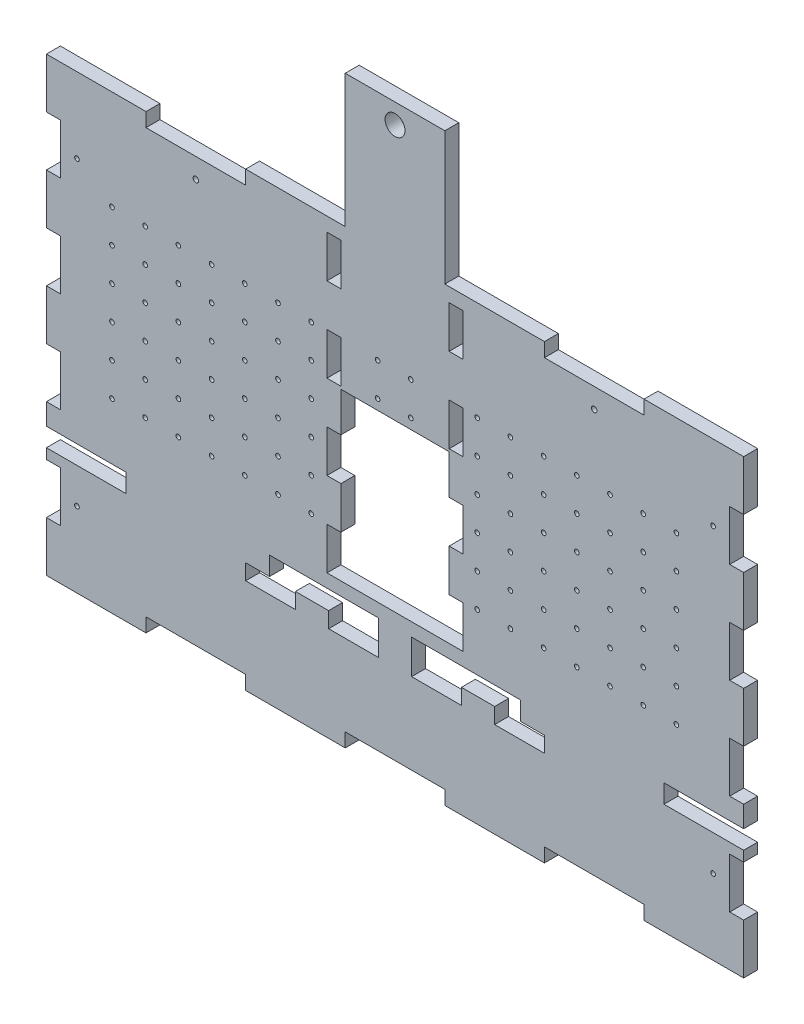
SolidWorks part; units mm, degrees
ref_plane "Front Plane" through (0, 0, 0) normal (0, 0, 1) x (1, 0, 0)
ref_plane "Top Plane" through (0, 0, 0) normal (0, 1, 0) x (1, 0, 0)
ref_plane "Right Plane" through (0, 0, 0) normal (1, 0, 0) x (0, 0, -1)
sketch "Sketch1" plane through (0, 0, 0) normal (0, 0, 1) x (1, 0, 0)
  line L1 (-127.8759, 88.4641) -> (138.8241, 88.4641)
  line L2 (-127.8759, 88.4641) -> (-127.8759, -84.2559)
  line L3 (-127.8759, -84.2559) -> (138.8241, -84.2559)
  line L4 (138.8241, 88.4641) -> (138.8241, -84.2559)
  dimension "D1" = 266.7
  dimension "D2" = 172.72
extrude "Boss-Extrude1" add sketch "Sketch1" along normal blind 5.334
sketch "Sketch2" plane through (0, 0, 5.334) normal (0, 0, 1) x (1, 0, 0)
  line L0 (-127.8759, -84.2559) -> (138.8241, -84.2559) construction
  line L1 (-89.7759, -84.2559) -> (-51.6759, -84.2559)
  line L2 (-89.7759, -84.2559) -> (-89.7759, -78.9219)
  line L3 (-89.7759, -78.9219) -> (-51.6759, -78.9219)
  line L4 (-51.6759, -84.2559) -> (-51.6759, -78.9219)
  line L5 (-89.7759, -78.9219) -> (-127.8759, -78.9219) construction
  line L6 (-13.5759, -84.2559) -> (24.5241, -84.2559)
  line L7 (-13.5759, -84.2559) -> (-13.5759, -78.9219)
  line L8 (-13.5759, -78.9219) -> (24.5241, -78.9219)
  line L9 (24.5241, -84.2559) -> (24.5241, -78.9219)
  line L10 (62.6241, -84.2559) -> (100.7241, -84.2559)
  line L11 (62.6241, -84.2559) -> (62.6241, -78.9219)
  line L12 (62.6241, -78.9219) -> (100.7241, -78.9219)
  line L13 (100.7241, -84.2559) -> (100.7241, -78.9219)
  line L14 (-127.8759, 88.4641) -> (-127.8759, -84.2559) construction
  line L15 (-51.6759, -78.9219) -> (-13.5759, -78.9219) construction
  line L16 (24.5241, -78.9219) -> (62.6241, -78.9219) construction
  line L17 (62.6241, -78.9219) -> (62.364, -79.7896) construction
  line L18 (100.7241, -78.9219) -> (138.8241, -78.9219) construction
  line L19 (138.8241, -84.2559) -> (138.8241, 88.4641) construction
  line L20 (-127.8759, 2.1041) -> (138.8241, 2.1041) construction
  line L21 (100.7241, 88.4641) -> (100.7241, 83.1301)
  line L22 (62.6241, 83.1301) -> (100.7241, 83.1301)
  line L23 (62.6241, 88.4641) -> (62.6241, 83.1301)
  line L24 (24.5241, 88.4641) -> (24.5241, 83.1301)
  line L25 (-13.5759, 83.1301) -> (24.5241, 83.1301)
  line L26 (-13.5759, 88.4641) -> (-13.5759, 83.1301)
  line L27 (-51.6759, 88.4641) -> (-51.6759, 83.1301)
  line L28 (-89.7759, 83.1301) -> (-51.6759, 83.1301)
  line L29 (-89.7759, 88.4641) -> (-89.7759, 83.1301)
  line L30 (62.6241, 88.4641) -> (100.7241, 88.4641)
  line L31 (-13.5759, 88.4641) -> (24.5241, 88.4641)
  line L32 (-89.7759, 88.4641) -> (-51.6759, 88.4641)
  dimension "D1" = 5.334
extrude "Cut-Extrude1" cut sketch "Sketch2" against normal through all
sketch "Sketch5" plane through (0, 0, 5.334) normal (0, 0, 1) x (1, 0, 0)
  line L0 (5.4741, 83.1301) -> (5.4741, -78.9219) construction
  line L1 (-13.5759, 83.1301) -> (24.5241, 83.1301) construction
  line L2 (24.5241, -78.9219) -> (-13.5759, -78.9219) construction
  line L3 (11.8241, -34.8224) -> (11.8241, -41.9344)
  line L4 (-42.5319, -34.8224) -> (-0.8759, -34.8224)
  line L5 (-42.5319, -34.8224) -> (-42.5319, -41.9344)
  line L6 (-42.5319, -41.9344) -> (-0.8759, -41.9344)
  line L7 (-0.8759, -34.8224) -> (-0.8759, -41.9344)
  line L8 (53.4801, -41.9344) -> (11.8241, -41.9344)
  line L9 (53.4801, -34.8224) -> (53.4801, -41.9344)
  line L10 (53.4801, -34.8224) -> (11.8241, -34.8224)
  line L11 (11.8241, -34.8224) -> (-0.8759, -34.8224) construction
  line L12 (-0.8759, -41.9344) -> (11.8241, -41.9344) construction
  line L13 (-139.0519, -34.8224) -> (-97.3959, -34.8224)
  line L14 (-139.0519, -34.8224) -> (-139.0519, -41.9344)
  line L15 (-139.0519, -41.9344) -> (-97.3959, -41.9344)
  line L16 (-97.3959, -34.8224) -> (-97.3959, -41.9344)
  line L18 (108.3441, -34.8224) -> (108.3441, -41.9344)
  line L19 (150.0001, -41.9344) -> (108.3441, -41.9344)
  line L20 (150.0001, -34.8224) -> (150.0001, -41.9344)
  line L21 (150.0001, -34.8224) -> (108.3441, -34.8224)
  dimension "D2" = 41.656
  dimension "D3" = 6.35
  dimension "D1" = 7.112
  dimension "D4" = 2
extrude "Cut-Extrude3" cut sketch "Sketch5" against normal through all
sketch "Sketch9" plane through (0, 0, 5.334) normal (0, 0, 1) x (1, 0, 0)
  line L0 (-127.8759, 88.4641) -> (-127.8759, -34.8224) construction
  line L1 (-127.8759, -65.0647) -> (-122.5419, -65.0647)
  line L2 (-127.8759, -65.0647) -> (-127.8759, -45.8736)
  line L3 (-127.8759, -45.8736) -> (-122.5419, -45.8736)
  line L4 (-122.5419, -65.0647) -> (-122.5419, -45.8736)
  line L5 (-122.5419, 69.273) -> (-122.5419, 88.4641) construction
  line L6 (-127.8759, -26.6825) -> (-122.5419, -26.6825)
  line L7 (-127.8759, -26.6825) -> (-127.8759, -7.4914)
  line L8 (-127.8759, -7.4914) -> (-122.5419, -7.4914)
  line L9 (-122.5419, -26.6825) -> (-122.5419, -7.4914)
  line L10 (-127.8759, 11.6997) -> (-122.5419, 11.6997)
  line L11 (-127.8759, 11.6997) -> (-127.8759, 30.8908)
  line L12 (-127.8759, 30.8908) -> (-122.5419, 30.8908)
  line L13 (-122.5419, 11.6997) -> (-122.5419, 30.8908)
  line L14 (-127.8759, 50.0819) -> (-122.5419, 50.0819)
  line L15 (-127.8759, 50.0819) -> (-127.8759, 69.273)
  line L16 (-127.8759, 69.273) -> (-122.5419, 69.273)
  line L17 (-122.5419, 50.0819) -> (-122.5419, 69.273)
  line L18 (-89.7759, 88.4641) -> (-127.8759, 88.4641) construction
  line L19 (-122.5419, 50.0819) -> (-122.5419, 30.8908) construction
  line L20 (-122.5419, 11.6997) -> (-122.5419, -7.4914) construction
  line L21 (-122.5419, -26.6825) -> (-122.5419, -45.8736) construction
  line L22 (-122.5419, -65.0647) -> (-122.5419, -84.2559) construction
  line L23 (-127.8759, -84.2559) -> (-89.7759, -84.2559) construction
  line L24 (5.4741, 83.1301) -> (5.4741, -78.9219) construction
  line L25 (-13.5759, 83.1301) -> (24.5241, 83.1301) construction
  line L26 (24.5241, -78.9219) -> (-13.5759, -78.9219) construction
  line L27 (133.4901, -65.0647) -> (133.4901, -84.2559) construction
  line L28 (133.4901, -26.6825) -> (133.4901, -45.8736) construction
  line L29 (133.4901, 11.6997) -> (133.4901, -7.4914) construction
  line L30 (133.4901, 50.0819) -> (133.4901, 30.8908) construction
  line L31 (133.4901, 69.273) -> (133.4901, 88.4641) construction
  line L32 (133.4901, 50.0819) -> (133.4901, 69.273)
  line L33 (138.8241, 69.273) -> (133.4901, 69.273)
  line L34 (138.8241, 50.0819) -> (138.8241, 69.273)
  line L35 (138.8241, 50.0819) -> (133.4901, 50.0819)
  line L36 (133.4901, 11.6997) -> (133.4901, 30.8908)
  line L37 (138.8241, 30.8908) -> (133.4901, 30.8908)
  line L38 (138.8241, 11.6997) -> (138.8241, 30.8908)
  line L39 (138.8241, 11.6997) -> (133.4901, 11.6997)
  line L40 (133.4901, -26.6825) -> (133.4901, -7.4914)
  line L41 (138.8241, -7.4914) -> (133.4901, -7.4914)
  line L42 (138.8241, -26.6825) -> (138.8241, -7.4914)
  line L43 (138.8241, -26.6825) -> (133.4901, -26.6825)
  line L44 (133.4901, -65.0647) -> (133.4901, -45.8736)
  line L45 (138.8241, -45.8736) -> (133.4901, -45.8736)
  line L46 (138.8241, -65.0647) -> (138.8241, -45.8736)
  line L47 (138.8241, -65.0647) -> (133.4901, -65.0647)
  dimension "D1" = 5.334
extrude "Cut-Extrude7" cut sketch "Sketch9" against normal through all
sketch "Sketch10" plane through (0, 88.4641, 0) normal (0, 1, 0) x (1, 0, 0)
  line L1 (24.5241, -5.334) -> (62.6241, -5.334)
  line L2 (24.5241, -5.334) -> (24.5241, 0)
  line L3 (24.5241, 0) -> (62.6241, 0)
  line L4 (62.6241, -5.334) -> (62.6241, 0)
extrude "Boss-Extrude2" add sketch "Sketch10" along normal blind 50.8
sketch "Sketch11" plane through (0, 0, 0) normal (0, 0, -1) x (-1, 0, 0)
  line L0 (-24.5241, 83.1301) -> (-24.5241, 139.2641) construction
  line L1 (-24.5241, 88.4641) -> (-31.1281, 88.4641)
  line L2 (-24.5241, 88.4641) -> (-24.5241, 129.1041)
  line L3 (-24.5241, 129.1041) -> (-31.1281, 129.1041)
  line L4 (-31.1281, 88.4641) -> (-31.1281, 129.1041)
  line L5 (13.5759, 88.4641) -> (51.6759, 88.4641) construction
  dimension "D1" = 6.604
  dimension "D3" = 0
extrude "Cut-Extrude8" cut sketch "Sketch11" against normal through all
sketch "Sketch12" plane through (0, 0, 5.334) normal (0, 0, 1) x (1, 0, 0)
  line L0 (62.6241, 139.2641) -> (62.6241, 83.1301) construction
  circle A0 centre (43.5741, 130.4765) radius 3.81
  dimension "D1" = 19.05
extrude "Cut-Extrude9" cut sketch "Sketch12" against normal through all
sketch "Sketch14" plane through (0, 0, 5.334) normal (0, 0, 1) x (1, 0, 0)
  line L0 (-89.7759, 88.4641) -> (-127.8759, 88.4641) construction
  circle A0 centre (-102.7976, 50.3641) radius 0.889
  circle A1 centre (-90.0976, 50.3641) radius 0.889
  circle A2 centre (-77.3976, 50.3641) radius 0.889
  circle A3 centre (-64.6976, 50.3641) radius 0.889
  circle A4 centre (-51.9976, 50.3641) radius 0.889
  circle A5 centre (-39.2976, 50.3641) radius 0.889
  circle A6 centre (-26.5976, 50.3641) radius 0.889
  circle A8 centre (-1.1976, 50.3641) radius 0.889
  circle A9 centre (11.5024, 50.3641) radius 0.889
  circle A11 centre (36.9024, 50.3641) radius 0.889
  circle A12 centre (49.6024, 50.3641) radius 0.889
  circle A13 centre (62.3024, 50.3641) radius 0.889
  circle A14 centre (75.0024, 50.3641) radius 0.889
  circle A15 centre (87.7024, 50.3641) radius 0.889
  circle A16 centre (100.4024, 50.3641) radius 0.889
  circle A17 centre (113.1024, 50.3641) radius 0.889
  circle A18 centre (-102.7976, 37.6641) radius 0.889
  circle A19 centre (-90.0976, 37.6641) radius 0.889
  circle A20 centre (-77.3976, 37.6641) radius 0.889
  circle A21 centre (-64.6976, 37.6641) radius 0.889
  circle A22 centre (-51.9976, 37.6641) radius 0.889
  circle A23 centre (-39.2976, 37.6641) radius 0.889
  circle A24 centre (-26.5976, 37.6641) radius 0.889
  circle A26 centre (-1.1976, 37.6641) radius 0.889
  circle A27 centre (11.5024, 37.6641) radius 0.889
  circle A29 centre (36.9024, 37.6641) radius 0.889
  circle A30 centre (49.6024, 37.6641) radius 0.889
  circle A31 centre (62.3024, 37.6641) radius 0.889
  circle A32 centre (75.0024, 37.6641) radius 0.889
  circle A33 centre (87.7024, 37.6641) radius 0.889
  circle A34 centre (100.4024, 37.6641) radius 0.889
  circle A35 centre (113.1024, 37.6641) radius 0.889
  circle A36 centre (-102.7976, 24.9641) radius 0.889
  circle A37 centre (-90.0976, 24.9641) radius 0.889
  circle A38 centre (-77.3976, 24.9641) radius 0.889
  circle A39 centre (-64.6976, 24.9641) radius 0.889
  circle A40 centre (-51.9976, 24.9641) radius 0.889
  circle A41 centre (-39.2976, 24.9641) radius 0.889
  circle A42 centre (-26.5976, 24.9641) radius 0.889
  circle A44 centre (-1.1976, 24.9641) radius 0.889
  circle A45 centre (11.5024, 24.9641) radius 0.889
  circle A47 centre (36.9024, 24.9641) radius 0.889
  circle A48 centre (49.6024, 24.9641) radius 0.889
  circle A49 centre (62.3024, 24.9641) radius 0.889
  circle A50 centre (75.0024, 24.9641) radius 0.889
  circle A51 centre (87.7024, 24.9641) radius 0.889
  circle A52 centre (100.4024, 24.9641) radius 0.889
  circle A53 centre (113.1024, 24.9641) radius 0.889
  circle A54 centre (-102.7976, 12.2641) radius 0.889
  circle A55 centre (-90.0976, 12.2641) radius 0.889
  circle A56 centre (-77.3976, 12.2641) radius 0.889
  circle A57 centre (-64.6976, 12.2641) radius 0.889
  circle A58 centre (-51.9976, 12.2641) radius 0.889
  circle A59 centre (-39.2976, 12.2641) radius 0.889
  circle A60 centre (-26.5976, 12.2641) radius 0.889
  circle A65 centre (36.9024, 12.2641) radius 0.889
  circle A66 centre (49.6024, 12.2641) radius 0.889
  circle A67 centre (62.3024, 12.2641) radius 0.889
  circle A68 centre (75.0024, 12.2641) radius 0.889
  circle A69 centre (87.7024, 12.2641) radius 0.889
  circle A70 centre (100.4024, 12.2641) radius 0.889
  circle A71 centre (113.1024, 12.2641) radius 0.889
  circle A72 centre (-102.7976, -0.4359) radius 0.889
  circle A73 centre (-90.0976, -0.4359) radius 0.889
  circle A74 centre (-77.3976, -0.4359) radius 0.889
  circle A75 centre (-64.6976, -0.4359) radius 0.889
  circle A76 centre (-51.9976, -0.4359) radius 0.889
  circle A77 centre (-39.2976, -0.4359) radius 0.889
  circle A78 centre (-26.5976, -0.4359) radius 0.889
  circle A79 centre (-13.8976, -0.4359) radius 0.889
  circle A80 centre (-1.1976, -0.4359) radius 0.889
  circle A81 centre (11.5024, -0.4359) radius 0.889
  circle A82 centre (24.2024, -0.4359) radius 0.889
  circle A83 centre (36.9024, -0.4359) radius 0.889
  circle A84 centre (49.6024, -0.4359) radius 0.889
  circle A85 centre (62.3024, -0.4359) radius 0.889
  circle A86 centre (75.0024, -0.4359) radius 0.889
  circle A87 centre (87.7024, -0.4359) radius 0.889
  circle A88 centre (100.4024, -0.4359) radius 0.889
  circle A89 centre (113.1024, -0.4359) radius 0.889
  circle A90 centre (-102.7976, -13.1359) radius 0.889
  circle A91 centre (-90.0976, -13.1359) radius 0.889
  circle A92 centre (-77.3976, -13.1359) radius 0.889
  circle A93 centre (-64.6976, -13.1359) radius 0.889
  circle A94 centre (-51.9976, -13.1359) radius 0.889
  circle A95 centre (-39.2976, -13.1359) radius 0.889
  circle A96 centre (-26.5976, -13.1359) radius 0.889
  circle A97 centre (-13.8976, -13.1359) radius 0.889
  circle A98 centre (-1.1976, -13.1359) radius 0.889
  circle A99 centre (11.5024, -13.1359) radius 0.889
  circle A100 centre (24.2024, -13.1359) radius 0.889
  circle A101 centre (36.9024, -13.1359) radius 0.889
  circle A102 centre (49.6024, -13.1359) radius 0.889
  circle A103 centre (62.3024, -13.1359) radius 0.889
  circle A104 centre (75.0024, -13.1359) radius 0.889
  circle A105 centre (87.7024, -13.1359) radius 0.889
  circle A106 centre (100.4024, -13.1359) radius 0.889
  circle A107 centre (113.1024, -13.1359) radius 0.889
  circle A108 centre (-1.1976, 12.2641) radius 0.889 [skipped]
  circle A110 centre (11.5024, 12.2641) radius 0.889 [skipped]
  circle A116 centre (24.2024, 50.3641) radius 0.889 [skipped]
  circle A117 centre (-13.8976, 50.3641) radius 0.889 [skipped]
  dimension "D1" = 18
  dimension "D2" = 38.1
  dimension "D4" = 1.778
  dimension "D3" = 6
extrude "Cut-Extrude11" cut sketch "Sketch14" against normal through all
sketch "Sketch15" plane through (0, 0, 5.334) normal (0, 0, 1) x (1, 0, 0)
  line L1 (31.1281, 129.1041) -> (24.5241, 129.1041)
  line L2 (31.1281, 129.1041) -> (31.1281, 139.2641)
  line L3 (31.1281, 139.2641) -> (24.5241, 139.2641)
  line L4 (24.5241, 129.1041) -> (24.5241, 139.2641)
extrude "Cut-Extrude12" cut sketch "Sketch15" against normal through all
sketch "Sketch16" plane through (0, 0, 5.334) normal (0, 0, 1) x (1, 0, 0)
  line L0 (5.4741, 83.1301) -> (5.4741, -78.9219) construction
  line L1 (-15.2269, 33.7576) -> (26.1751, 33.7576)
  line L2 (-15.2269, 33.7576) -> (-15.2269, -29.7424)
  line L3 (-15.2269, -29.7424) -> (26.1751, -29.7424)
  line L4 (26.1751, 33.7576) -> (26.1751, -29.7424)
  line L5 (-13.5759, 83.1301) -> (24.5241, 83.1301) construction
  line L6 (24.5241, -78.9219) -> (-13.5759, -78.9219) construction
  line L8 (-0.8759, -34.8224) -> (-42.5319, -34.8224) construction
  dimension "D1" = 63.5
  dimension "D2" = 41.402
  dimension "D3" = 20.701
  dimension "D4" = 5.08
extrude "Cut-Extrude13" cut sketch "Sketch16" against normal through all
sketch "Sketch17" plane through (0, 0, 5.334) normal (0, 0, 1) x (1, 0, 0)
  line L0 (-15.2269, 33.7576) -> (-15.2269, -29.7424) construction
  line L1 (-15.2269, -29.7424) -> (-20.5609, -29.7424)
  line L2 (-15.2269, -29.7424) -> (-15.2269, -13.6178)
  line L3 (-15.2269, -13.6178) -> (-20.5609, -13.6178)
  line L4 (-20.5609, -29.7424) -> (-20.5609, -13.6178)
  line L5 (-15.2269, 2.5069) -> (-20.5609, 2.5069)
  line L6 (-15.2269, 2.5069) -> (-15.2269, 18.6315)
  line L7 (-15.2269, 18.6315) -> (-20.5609, 18.6315)
  line L8 (-20.5609, 2.5069) -> (-20.5609, 18.6315)
  line L9 (-20.5609, -13.6178) -> (-20.5609, 2.5069) construction
  line L10 (-20.5609, 50.8808) -> (-15.2269, 50.8808)
  line L11 (-20.5609, 50.8808) -> (-20.5609, 34.7562)
  line L12 (-20.5609, 34.7562) -> (-15.2269, 34.7562)
  line L13 (-15.2269, 50.8808) -> (-15.2269, 34.7562)
  line L14 (-20.5609, 67.0055) -> (-15.2269, 67.0055)
  line L15 (-20.5609, 67.0055) -> (-20.5609, 83.1301)
  line L16 (-20.5609, 83.1301) -> (-15.2269, 83.1301)
  line L17 (-15.2269, 67.0055) -> (-15.2269, 83.1301)
  line L18 (-20.5609, 18.6315) -> (-20.5609, 34.7562) construction
  line L19 (-20.5609, 67.0055) -> (-20.5609, 50.8808) construction
  line L20 (5.4741, 83.1301) -> (5.4741, -78.9219) construction
  line L21 (-13.5759, 83.1301) -> (24.5241, 83.1301) construction
  line L22 (24.5241, -78.9219) -> (-13.5759, -78.9219) construction
  line L23 (31.5091, 67.0055) -> (31.5091, 50.8808) construction
  line L24 (31.5091, 18.6315) -> (31.5091, 34.7562) construction
  line L25 (31.5091, -13.6178) -> (31.5091, 2.5069) construction
  line L26 (26.1751, 67.0055) -> (26.1751, 83.1301)
  line L27 (31.5091, 83.1301) -> (26.1751, 83.1301)
  line L28 (31.5091, 67.0055) -> (31.5091, 83.1301)
  line L29 (31.5091, 67.0055) -> (26.1751, 67.0055)
  line L30 (26.1751, 50.8808) -> (26.1751, 34.7562)
  line L31 (31.5091, 34.7562) -> (26.1751, 34.7562)
  line L32 (31.5091, 50.8808) -> (31.5091, 34.7562)
  line L33 (31.5091, 50.8808) -> (26.1751, 50.8808)
  line L34 (31.5091, 2.5069) -> (31.5091, 18.6315)
  line L35 (26.1751, 18.6315) -> (31.5091, 18.6315)
  line L36 (26.1751, 2.5069) -> (26.1751, 18.6315)
  line L37 (26.1751, 2.5069) -> (31.5091, 2.5069)
  line L38 (31.5091, -29.7424) -> (31.5091, -13.6178)
  line L39 (26.1751, -13.6178) -> (31.5091, -13.6178)
  line L40 (26.1751, -29.7424) -> (26.1751, -13.6178)
  line L41 (26.1751, -29.7424) -> (31.5091, -29.7424)
  dimension "D1" = 0
  dimension "D2" = 5.334
  dimension "D3" = 5.334
  dimension "D4" = 5.334
extrude "Cut-Extrude14" cut sketch "Sketch17" against normal through all
sketch "Sketch18" plane through (0, 0, 5.334) normal (0, 0, 1) x (1, 0, 0)
  line L0 (24.5241, 83.1301) -> (24.5241, 148.9274) construction
  line L1 (31.1281, 139.2641) -> (62.6241, 139.2641) construction
  line L2 (-13.5759, 83.1301) -> (24.5241, 83.1301)
  line L3 (-13.5759, 83.1301) -> (-13.5759, 139.2641)
  line L4 (-13.5759, 139.2641) -> (24.5241, 139.2641)
  line L5 (24.5241, 83.1301) -> (24.5241, 139.2641)
  dimension "D1" = 0
extrude "Boss-Extrude3" add sketch "Sketch18" against normal blind 5.334
sketch "Sketch19" plane through (0, 0, 5.334) normal (0, 0, 1) x (1, 0, 0)
  line L1 (31.1281, 88.4641) -> (65.8849, 88.4641)
  line L2 (31.1281, 88.4641) -> (31.1281, 143.4078)
  line L3 (31.1281, 143.4078) -> (65.8849, 143.4078)
  line L4 (65.8849, 88.4641) -> (65.8849, 143.4078)
extrude "Cut-Extrude15" cut sketch "Sketch19" against normal through all
sketch "Sketch20" plane through (0, 0, 5.334) normal (0, 0, 1) x (1, 0, 0)
  line L0 (5.4741, 139.2641) -> (5.4741, 29.9476) construction
  line L1 (24.5241, 139.2641) -> (-13.5759, 139.2641) construction
  circle A0 centre (5.4741, 131.6441) radius 3.81
  dimension "D1" = 7.62
  dimension "D3" = 7.62
  dimension "D2" = 0
extrude "Cut-Extrude16" cut sketch "Sketch20" against normal through all contours A0
sketch "Sketch21" plane through (0, 0, 5.334) normal (0, 0, 1) x (1, 0, 0)
  line L0 (133.4901, 59.6775) -> (-122.5419, 59.6775) construction
  line L1 (133.4901, 69.273) -> (133.4901, 50.0819) construction
  line L2 (-122.5419, 50.0819) -> (-122.5419, 69.273) construction
  line L3 (-122.5419, -55.4692) -> (133.4901, -55.4692) construction
  line L4 (-122.5419, -65.0647) -> (-122.5419, -45.8736) construction
  line L5 (133.4901, -45.8736) -> (133.4901, -65.0647) construction
  line L6 (138.8241, 2.1041) -> (-127.8759, 2.1041) construction
  line L7 (138.8241, -7.4914) -> (138.8241, 11.6997) construction
  line L8 (-127.8759, 11.6997) -> (-127.8759, -7.4914) construction
  line L9 (5.4741, 139.2641) -> (5.4741, -78.9219) construction
  line L10 (24.5241, 139.2641) -> (-13.5759, 139.2641) construction
  line L11 (24.5241, -78.9219) -> (-13.5759, -78.9219) construction
  circle A0 centre (127.1401, 59.6775) radius 0.889
  circle A1 centre (-116.1919, 59.6775) radius 0.889
  circle A2 centre (-116.1919, -55.4692) radius 0.889
  circle A3 centre (127.1401, -55.4692) radius 0.889
  dimension "D1" = 1.778
  dimension "D2" = 0
  dimension "D3" = 6.35
extrude "Cut-Extrude17" cut sketch "Sketch21" against normal through all
sketch "Sketch22" plane through (0, 0, 0) normal (0, 0, -1) x (-1, 0, 0)
  line L0 (-11.8241, -41.9344) -> (-53.4801, -41.9344) construction
  line L1 (-30.8741, -41.9344) -> (-11.8241, -41.9344)
  line L2 (-30.8741, -41.9344) -> (-30.8741, -47.9281)
  line L3 (-30.8741, -47.9281) -> (-11.8241, -47.9281)
  line L4 (-11.8241, -41.9344) -> (-11.8241, -47.9281)
  line L5 (-11.8241, -34.8224) -> (-11.8241, -41.9344) construction
  line L6 (-62.6241, -47.9281) -> (-43.5741, -47.9281)
  line L7 (-43.5741, -41.9344) -> (-43.5741, -47.9281)
  line L8 (-62.6241, -41.9344) -> (-43.5741, -41.9344)
  line L9 (-62.6241, -41.9344) -> (-62.6241, -47.9281)
  line L10 (-5.4741, -78.9219) -> (-5.4741, 95.0308) construction
  line L11 (-24.5241, -78.9219) -> (13.5759, -78.9219) construction
  line L12 (51.6759, -41.9344) -> (51.6759, -47.9281)
  line L13 (51.6759, -41.9344) -> (32.6259, -41.9344)
  line L14 (32.6259, -41.9344) -> (32.6259, -47.9281)
  line L15 (51.6759, -47.9281) -> (32.6259, -47.9281)
  line L16 (0.8759, -41.9344) -> (0.8759, -47.9281)
  line L17 (19.9259, -47.9281) -> (0.8759, -47.9281)
  line L18 (19.9259, -41.9344) -> (19.9259, -47.9281)
  line L19 (19.9259, -41.9344) -> (0.8759, -41.9344)
  dimension "D1" = 19.05
  dimension "D2" = 0
  dimension "D3" = 2
extrude "Cut-Extrude18" cut sketch "Sketch22" against normal through all
sketch "Sketch23" plane through (0, 0, 0) normal (0, 0, -1) x (-1, 0, 0)
  line L0 (-81.6741, 83.1301) -> (-81.6741, 61.0847) construction
  line L1 (-62.6241, 83.1301) -> (-100.7241, 83.1301) construction
  line L2 (-5.4741, 139.2641) -> (-5.4741, 93.6801) construction
  line L3 (-24.5241, 139.2641) -> (13.5759, 139.2641) construction
  circle A0 centre (-81.6741, 75.5101) radius 1.0477
  circle A1 centre (70.7259, 75.5101) radius 1.0477
  dimension "D1" = 2.0955
  dimension "D2" = 0
  dimension "D3" = 7.62
extrude "Cut-Extrude19" cut sketch "Sketch23" against normal through all
equation "\"MDF\"= .21in"
equation "\"Foamcore\"= .13in"
equation "\"Gmaterial\"= \"MDF\""
equation "\"D1@Boss-Extrude1\"=\"MDF\""
equation "\"D1@Sketch2\"=\"MDF\""
equation "\"D1@Sketch5\"=\"MDF\"+0.07"
equation "\"D1@Sketch9\"=\"MDF\""
equation "\"D1@Sketch11\"=\"MDF\"+.05"
equation "\"D2@Sketch17\"=\"MDF\""
equation "\"D3@Sketch17\"=\"MDF\""
equation "\"D4@Sketch17\"=\"MDF\""
equation "\"D1@Boss-Extrude3\"=\"MDF\""
